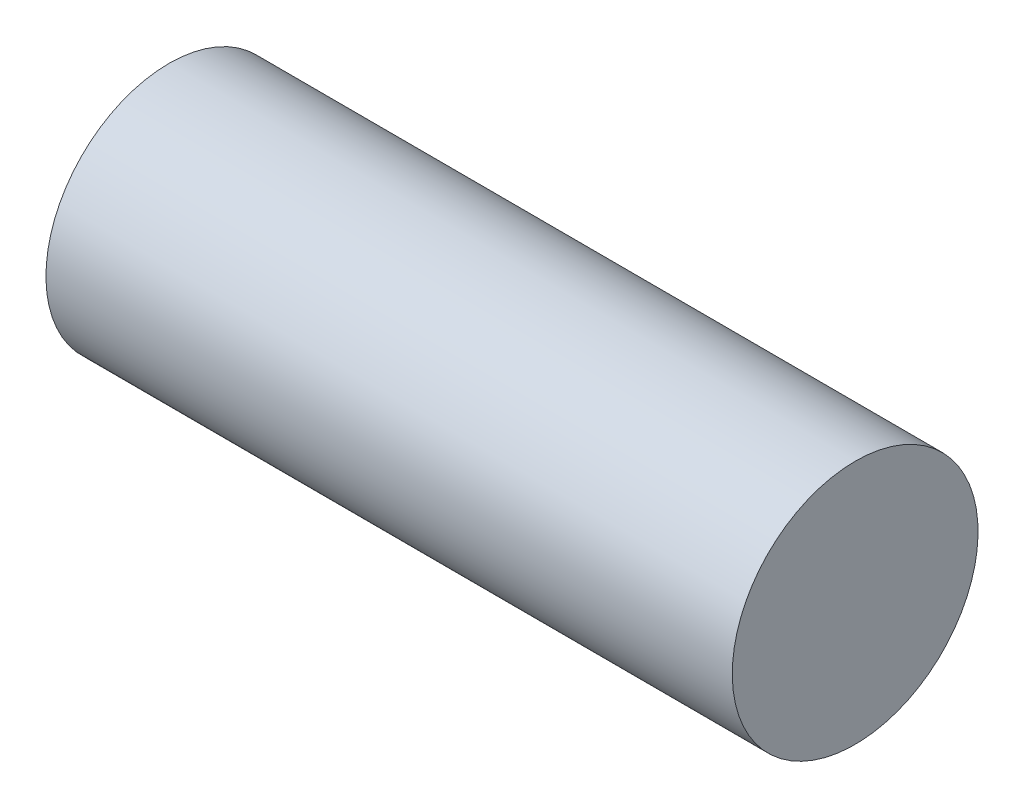
SolidWorks part; units mm, degrees
material "Custom Plastic"
ref_plane "X-Y Datum" through (0, 0, 0) normal (0, 0, 1) x (1, 0, 0)
ref_plane "X-Z Datum" through (0, 0, 0) normal (0, 1, 0) x (1, 0, 0)
ref_plane "Y-Z Datum" through (0, 0, 0) normal (1, 0, 0) x (0, 0, -1)
sketch3d "3DSketch1"
  line L0 (29.0347, 200.8567, 163.3218) -> (11.5347, 200.8445, 163.3218) construction
  line L1 (-13.6473, 200.895, 163.3218) -> (-6.7095, 200.8998, 163.3218) construction
  line L2 (-13.558, 200.8951, 163.3218) -> (12.6858, 200.8453, 163.3218)
  point P0 (12.6858, 200.8453, 163.3218)
  point P1 (-13.558, 200.8951, 163.3218)
sweep "Sweep1" add path "3DSketch1" circular profile diameter 9.398 parameters "D3"=9.398
